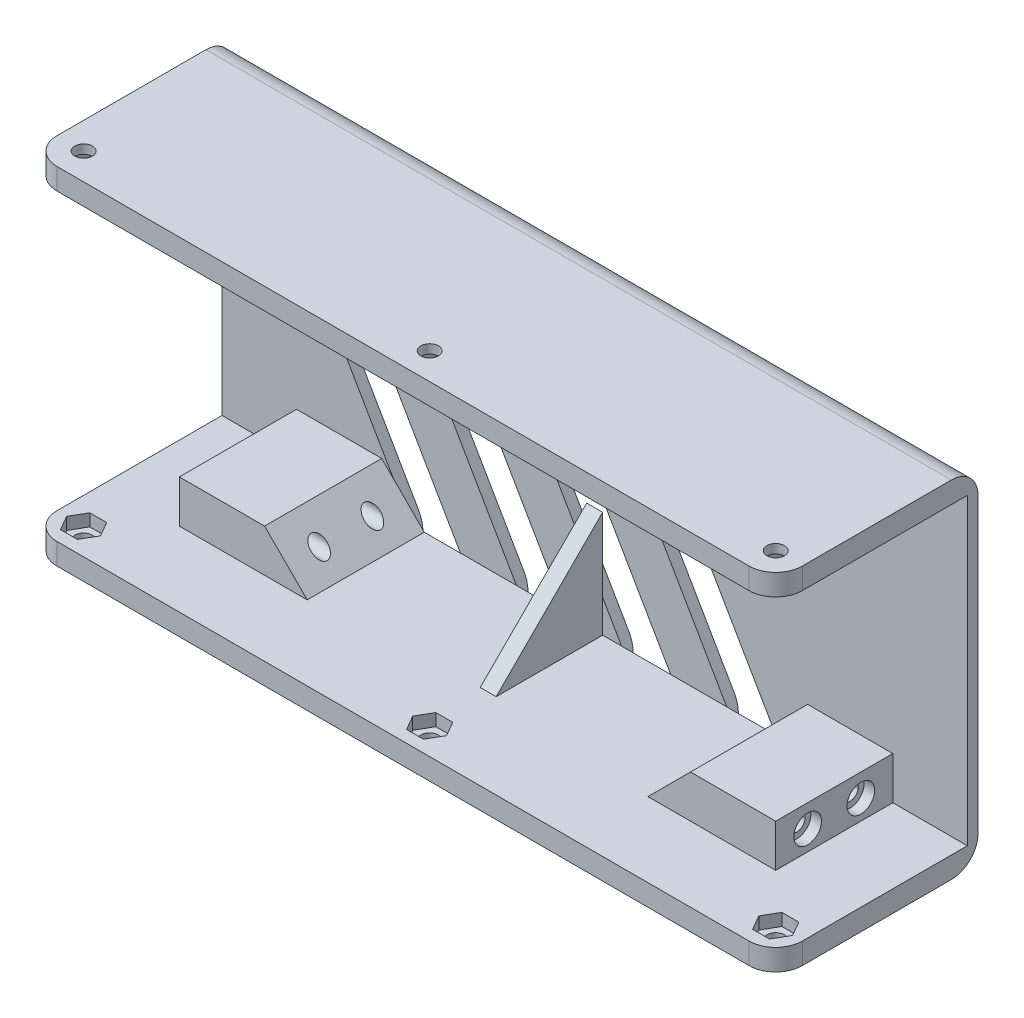
SolidWorks part; units mm, degrees
ref_plane "Front Plane" through (0, 0, 0) normal (0, 0, 1) x (1, 0, 0)
ref_plane "Top Plane" through (0, 0, 0) normal (0, 1, 0) x (1, 0, 0)
ref_plane "Right Plane" through (0, 0, 0) normal (1, 0, 0) x (0, 0, -1)
sketch "Sketch2" plane through (0, 0, 0) normal (0, 0, 1) x (1, 0, 0)
  line L1 (0, 0) -> (140, 0)
  line L2 (0, 0) -> (0, 65)
  line L3 (0, 65) -> (140, 65)
  line L4 (140, 0) -> (140, 65)
  dimension "D1" = 140
  dimension "D2" = 65
extrude "Boss-Extrude1" add sketch "Sketch2" along normal blind 38
sketch "Sketch3" plane through (0, 0, 38) normal (0, 0, 1) x (1, 0, 0)
  line L0 (126, 53) -> (126, 61)
  line L1 (112, 53) -> (126, 53)
  line L3 (112, 12) -> (126, 12)
  line L4 (126, 53) -> (126, 12)
  line L5 (126, 61) -> (140, 61)
  line L6 (140, 0) -> (140, 65) construction
  line L7 (126, 12) -> (126, 4)
  line L8 (126, 4) -> (140, 4)
  line L9 (140, 61) -> (140, 4)
  line L10 (140, 0) -> (140, 65)
  line L11 (70, 65) -> (70, 0) construction
  line L12 (140, 65) -> (0, 65) construction
  line L13 (0, 61) -> (0, 4)
  line L14 (14, 4) -> (0, 4)
  line L15 (14, 12) -> (14, 4)
  line L16 (14, 61) -> (0, 61)
  line L17 (14, 53) -> (14, 12)
  line L18 (28, 12) -> (14, 12)
  line L19 (28, 12) -> (28, 4)
  line L20 (28, 53) -> (14, 53)
  line L21 (14, 53) -> (14, 61)
  line L22 (28, 4) -> (112, 4)
  line L24 (28, 53) -> (28, 61)
  line L25 (28, 61) -> (112, 61)
  line L26 (112, 61) -> (112, 53)
  line L27 (112, 4) -> (112, 12)
  point P9 (140, 32.5)
  point P11 (140, 32.5)
  line M9 (0, 65) -> (0, 0)
  line M11 (140, 0) -> (140, 65)
  dimension "D1" = 41
  dimension "D2" = 14
  dimension "D3" = 8
  dimension "D4" = 14
extrude "Cut-Extrude1" cut sketch "Sketch3" against normal offset from surface (36 mm away) 2 contours L17 L21 L16 L14 L15 M9 | L11 L25 L24 L20 L17 L18 L19 L22 | L25 L11 L22 L27 L3 L4 L1 L26 | L7 L8 L5 L0 L4 M11 region at (96.4151, 32.5, 38) region at (133, 32.5, 38) region at (43.5849, 32.5, 38) region at (7, 32.5, 38) up to face at (70, 32.5, 0)
fillet "Fillet1" radius 5 2 edges at (70, 0, 0) (70, 65, 0)
sketch "Sketch4" plane through (0, 0, 38) normal (0, 0, 1) x (1, 0, 0)
  line L1 (0, 61) -> (140, 61)
  line L2 (0, 61) -> (0, 4)
  line L3 (0, 4) -> (140, 4)
  line L4 (140, 61) -> (140, 4)
extrude "Cut-Extrude2" cut sketch "Sketch4" against normal offset from surface (14 mm away) 22 up to face at (70, 32.5, 2)
fillet "Fillet2" radius 5 4 edges at (0, 2, 38) (140, 2, 38) (140, 63, 38) (0, 63, 38)
chamfer "Chamfer1" distance 10 angle 45 4 edges at (112, 4, 13) (112, 61, 13) (28, 61, 13) (28, 4, 13)
ref_plane "Plane1" through (70, 0, 0) normal (-1, 0, 0) x (0, 0, 1)
sketch "Sketch8" plane through (0, 61, 0) normal (0, -1, 0) x (1, 0, 0)
  line L0 (5, 33) -> (135, 33) construction
  line L9 (8.1754, 33) -> (6.5877, 35.75)
  line L10 (6.5877, 35.75) -> (3.4123, 35.75)
  line L11 (3.4123, 35.75) -> (1.8246, 33)
  line L12 (1.8246, 33) -> (3.4123, 30.25)
  line L13 (3.4123, 30.25) -> (6.5877, 30.25)
  line L14 (6.5877, 30.25) -> (8.1754, 33)
  line L15 (138.1754, 33) -> (136.5877, 35.75)
  line L16 (136.5877, 35.75) -> (133.4123, 35.75)
  line L17 (133.4123, 35.75) -> (131.8246, 33)
  line L18 (131.8246, 33) -> (133.4123, 30.25)
  line L19 (133.4123, 30.25) -> (136.5877, 30.25)
  line L20 (136.5877, 30.25) -> (138.1754, 33)
  line L21 (73.1754, 33) -> (71.5877, 35.75)
  line L22 (71.5877, 35.75) -> (68.4123, 35.75)
  line L23 (68.4123, 35.75) -> (66.8246, 33)
  line L24 (66.8246, 33) -> (68.4123, 30.25)
  line L25 (68.4123, 30.25) -> (71.5877, 30.25)
  line L26 (71.5877, 30.25) -> (73.1754, 33)
  circle A0 centre (5, 33) radius 2.75 construction
  circle A1 centre (135, 33) radius 2.75 construction
  circle A2 centre (70, 33) radius 2.75 construction
  circle A3 centre (5, 33) radius 1.65
  circle A4 centre (70, 33) radius 1.65
  circle A5 centre (135, 33) radius 1.65
  point P20 (5, 30.25)
  dimension "D4" = 3.3
  dimension "D1" = 5.5
  dimension "D2" = 5.5
  dimension "D3" = 5.5
extrude "Cut-Extrude4" cut sketch "Sketch8<2>" against normal through all contours A3 | A4 | A5 region at (5, 61, 33) region at (70, 61, 33) region at (135, 61, 33)
sketch "Sketch8<2>" plane through (0, 61, 0) normal (0, -1, 0) x (1, 0, 0) same geometry as "Sketch8"
extrude "Cut-Extrude3" cut sketch "Sketch8" against normal blind 2.3
ref_plane "Plane2" through (0, 32.5, 0) normal (0, 1, 0) x (1, 0, 0)
mirror "Mirror1" about plane through (0, 32.5, 0) normal (0, 1, 0) of "Cut-Extrude4", "Cut-Extrude3"
sketch "Sketch10" plane through (126, 0, 0) normal (1, 0, 0) x (0, 0, -1)
  line L0 (-13, 57.25) -> (-13, 7.75) construction
  line L1 (-13, 12) -> (-13, 53) construction
  line L2 (-2, 12) -> (-24, 12) construction
  line L3 (-2, 53) -> (-24, 53) construction
  line L5 (-18, 57.25) -> (-8, 57.25) construction
  line L6 (-18, 7.75) -> (-8, 7.75) construction
  circle A0 centre (-18, 57.25) radius 1.5
  circle A1 centre (-8, 57.25) radius 1.5
  circle A2 centre (-8, 7.75) radius 1.5
  circle A3 centre (-18, 7.75) radius 1.5
  point P8 (-13, 57.25)
  point P11 (-13, 32.5)
  point P12 (-13, 32.5)
  point P15 (-13, 7.75)
  dimension "D4" = 3
  dimension "D1" = 49.5
  dimension "D2" = 10
  dimension "D3" = 10
extrude "Cut-Extrude5" cut sketch "Sketch10" against normal through all
sketch "Sketch6" plane through (70, 0, 0) normal (-1, 0, 0) x (0, 0, 1)
  line L0 (2, 41) -> (22, 61)
  line L2 (2, 61) -> (33, 61) construction
  line L3 (2, 24) -> (22, 4)
  line L4 (2, 4) -> (24, 4) construction
  line L5 (2, 41) -> (2, 61)
  line L6 (2, 61) -> (22, 61)
  line L7 (2, 24) -> (2, 4)
  line L8 (2, 4) -> (22, 4)
  line L9 (2, 61) -> (2, 4) construction
  dimension "D1" = 45
  dimension "D2" = 45
  dimension "D3" = 20
  dimension "D4" = 20
extrude "Boss-Extrude2" add sketch "Sketch6" along normal blind 1.5 and the other way blind 1.5 contours L7 L8 L3 | L0 L6 L5 region at (70, 10.6667, 8.6667)
sketch "Sketch11" plane through (126, 0, 0) normal (1, 0, 0) x (0, 0, -1)
  circle A0 centre (-18, 57.25) radius 2.6
  circle A1 centre (-8, 57.25) radius 2.6
  circle A2 centre (-8, 7.75) radius 2.6
  circle A3 centre (-18, 7.75) radius 2.6
  dimension "D1" = 5.2
extrude "Cut-Extrude6" cut sketch "Sketch11" against normal blind 2
mirror "Mirror2" about plane through (70, 0, 0) normal (-1, 0, 0) of "Cut-Extrude6"
sketch "Sketch12" plane through (0, 0, 0) normal (0, 0, -1) x (-1, 0, 0)
  line L0 (-106.3398, 0) -> (-85.154, 36.695)
  line L1 (0, 0) -> (-140, 0) construction
  line L3 (-76.3605, 35.9257) -> (-97.1022, 0)
  line L4 (-97.1022, 0) -> (-106.3398, 0)
  line L5 (-86.5913, 0) -> (-66.355, 35.0503)
  line L7 (-57.5616, 34.281) -> (-77.3537, 0)
  line L8 (-77.3537, 0) -> (-86.5913, 0)
  line L9 (-66.8428, 0) -> (-47.5561, 33.4056)
  line L11 (-38.7627, 32.6363) -> (-57.6052, 0)
  line L12 (-57.6052, 0) -> (-66.8428, 0)
  line L13 (-47.0943, 0) -> (-28.7572, 31.7609)
  line L15 (-19.9638, 30.9916) -> (-37.8567, 0)
  line L16 (-37.8567, 0) -> (-47.0943, 0)
  line L17 (-85.154, 36.695) -> (-76.3605, 35.9257)
  line L18 (-28.7572, 31.7609) -> (-19.9638, 30.9916)
  line L19 (-47.5561, 33.4056) -> (-38.7627, 32.6363)
  line L20 (-66.355, 35.0503) -> (-57.5616, 34.281)
  line L21 (-85.154, 36.695) -> (-67.3568, 36.695) construction
  dimension "D1" = 8
  dimension "D2" = 60
  dimension "D4" = 5
  dimension "D3" = 4
extrude "Cut-Extrude7" cut sketch "Sketch12" against normal up to surface (2 mm away) up to face at (70, 32.5, 2)
mirror "Mirror4" [suppressed] about plane through (0, 0, 0) normal (0, 0, 1) of bodies 111
delete or keep bodies "Body-Delete/Keep 1" [suppressed] type delete bodies bodies 111
